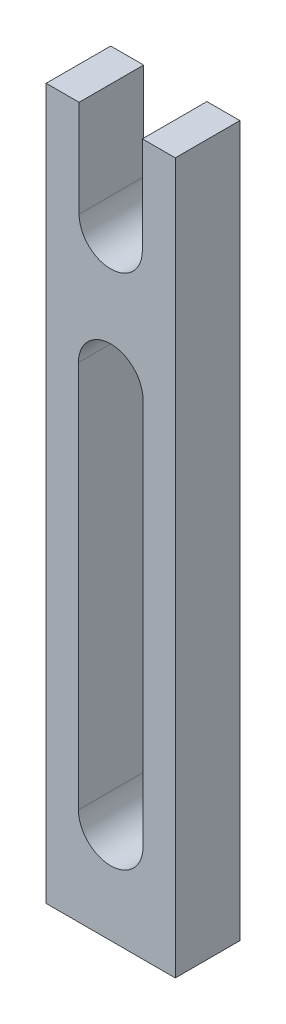
SolidWorks part; units mm, degrees
ref_plane "Front Plane" through (0, 0, 0) normal (0, 0, 1) x (1, 0, 0)
ref_plane "Top Plane" through (0, 0, 0) normal (0, 1, 0) x (1, 0, 0)
ref_plane "Right Plane" through (0, 0, 0) normal (1, 0, 0) x (0, 0, -1)
sketch "Sketch2" plane through (0, 0, 0) normal (0, 1, 0) x (1, 0, 0)
  line L1 (10, -5) -> (-10, -5)
  line L2 (10, -5) -> (10, 5)
  line L3 (10, 5) -> (-10, 5)
  line L4 (-10, -5) -> (-10, 5)
  line L5 (10, -5) -> (-10, 5) construction
  line L6 (10, 5) -> (-10, -5) construction
  point P0 (0, 0)
  dimension "D1" = 10
  dimension "D2" = 20
extrude "Boss-Extrude1" add sketch "Sketch2" along normal blind 110
sketch "Sketch3" plane through (0, 0, 5) normal (0, 0, 1) x (1, 0, 0)
  line L0 (-4.9, 110) -> (-4.9, 95)
  line L1 (-10, 110) -> (10, 110) construction
  line L2 (4.9, 95) -> (4.9, 110)
  line L3 (4.9, 110) -> (-4.9, 110)
  line L4 (-10, 0) -> (10, 0) construction
  arc A0 (-4.9, 95) -> (4.9, 95) centre (0, 95) ccw
  dimension "D2" = 4.9
  dimension "D1" = 95
extrude "Cut-Extrude1" cut sketch "Sketch3" against normal up to surface (10 mm away) up to face at (0, 55, -5)
sketch "Sketch5" plane through (0, 0, 5) normal (0, 0, 1) x (1, 0, 0)
  line L0 (0, 0) -> (0, 90.1) construction
  line L1 (-5, 15.05) -> (5, 15.05)
  line L2 (-5, 15.05) -> (-5, 75.05)
  line L3 (-5, 75.05) -> (5, 75.05)
  line L4 (5, 15.05) -> (5, 75.05)
  line L5 (-5, 15.05) -> (5, 75.05) construction
  line L6 (-5, 75.05) -> (5, 15.05) construction
  arc A0 (-5, 75.05) -> (5, 75.05) centre (0, 75.05) cw
  arc A1 (-5, 15.05) -> (5, 15.05) centre (0, 15.05) ccw
  arc A2 (-4.9, 95) -> (4.9, 95) centre (0, 95) ccw construction
  point P0 (0, 45.05)
  point P14 (0, 45.05)
  dimension "D1" = 5
  dimension "D2" = 60
extrude "Cut-Extrude2" cut sketch "Sketch5" against normal up to surface (10 mm away) contours L1 A1 | L1 L4 L3 L2 | A0 L3 region at (0, 45.05, 5) region at (0, 12.9279, 5) region at (0, 77.1721, 5) up to face at (0, 78.1375, -5)
sketch "Sketch6" plane through (0, 0, 0) normal (0, -1, 0) x (1, 0, 0)
  line L0 (-10, -5) -> (-10, 5) construction
  line L1 (10, 5) -> (10, -5) construction
  line L2 (-10, 0) -> (10, 0) construction
